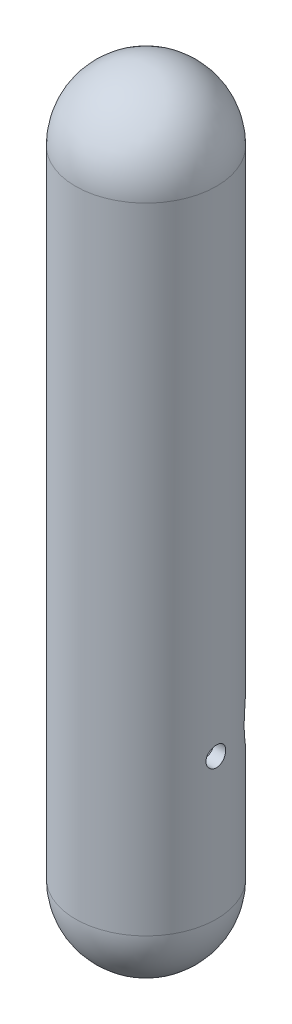
SolidWorks part; units mm, degrees
ref_plane "前视基准面" through (0, 0, 0) normal (0, 0, 1) x (1, 0, 0)
ref_plane "上视基准面" through (0, 0, 0) normal (0, 1, 0) x (1, 0, 0)
ref_plane "右视基准面" through (0, 0, 0) normal (1, 0, 0) x (0, 0, -1)
sketch "草图1" plane through (0, 0, 0) normal (0, 0, 1) x (1, 0, 0)
  line L0 (0, 0) -> (0, 110) construction
  line L2 (0, 110) -> (10, 110)
  line L3 (0, 110) -> (0, 0)
  line L4 (0, 0) -> (10, 0)
  line L5 (10, 110) -> (10, 0)
  dimension "D1" = 110
  dimension "D2" = 10
revolve "旋转1" add sketch "草图1" angle 360 about L0
sketch "草图2" plane through (0, 0, 0) normal (0, 0, 1) x (1, 0, 0)
  circle A0 centre (0, 30) radius 8.2
  dimension "D1" = 30
extrude "切除-拉伸1" cut sketch "草图2" against normal up to next and the other way blind 5
sketch "草图3" plane through (0, 0, 0) normal (1, 0, 0) x (0, 0, -1)
  line L0 (-5, 21.8) -> (-5, 38.2) construction
  circle A0 centre (0, 30) radius 1.4
  dimension "D1" = 5
  dimension "D2" = 30
extrude "切除-拉伸2" cut sketch "草图3" against normal through all and the other way through all
fillet "圆角1" radius 10 1 edges at (0, 0, -10)
fillet "圆角2" radius 10 1 edges at (0, 110, -10)
